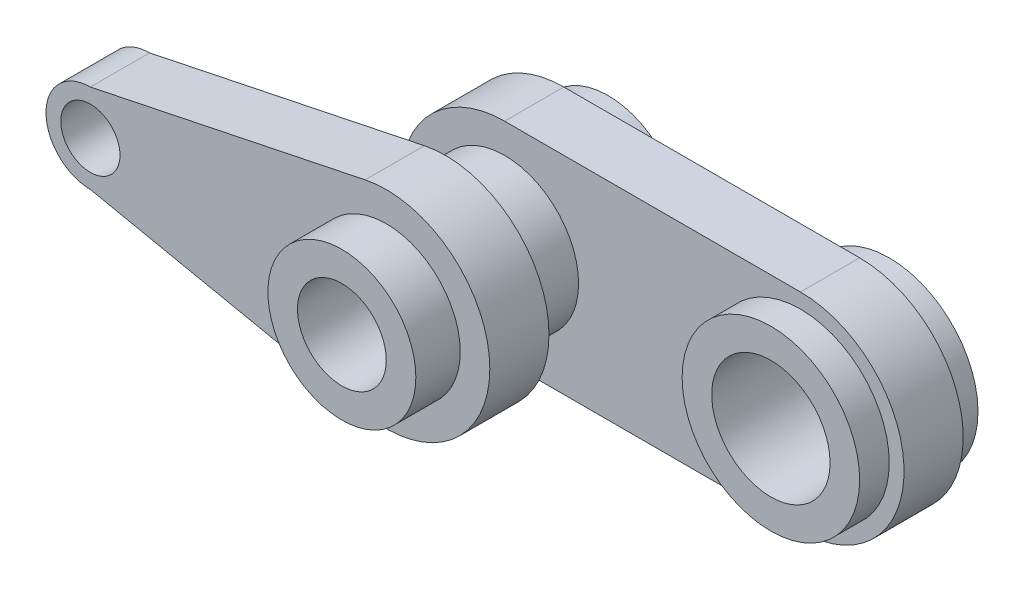
SolidWorks part; units mm, degrees
ref_plane "Front Plane" through (0, 0, 0) normal (0, 0, 1) x (1, 0, 0)
ref_plane "Top Plane" through (0, 0, 0) normal (0, 1, 0) x (1, 0, 0)
ref_plane "Right Plane" through (0, 0, 0) normal (1, 0, 0) x (0, 0, -1)
sketch "Sketch1" plane through (0, 0, 0) normal (0, 0, 1) x (1, 0, 0)
  line L0 (0, 0) -> (170, 0)
  line L1 (170, 0) -> (170, 70)
  line L2 (170, 70) -> (0, 70)
  line L3 (0, 70) -> (0, 0)
  dimension "D1" = 170
  dimension "D2" = 70
extrude "Boss-Extrude1" add sketch "Sketch1" along normal mid plane 20
fillet "Fillet1" 2 edges at (170, 70, 0) (170, 0, 0) type full round first side face at (85, 70, 0) second side face at (85, 0, 0) middle face at (170, 35, 0)
fillet "Fillet2" 2 edges at (0, 0, 0) (0, 70, 0) type full round first side face at (67.5, 0, 0) second side face at (67.5, 70, 0) middle face at (0, 35, 0)
sketch "Sketch2" plane through (0, 0, 10) normal (0, 0, 1) x (1, 0, 0)
  circle A0 centre (135, 35) radius 30
  dimension "D1" = 60
extrude "Boss-Extrude2" add sketch "Sketch2" along normal blind 10 and the other way blind 30
sketch "Sketch3" plane through (0, 0, 10) normal (0, 0, 1) x (1, 0, 0)
  circle A0 centre (35, 35) radius 25
  dimension "D1" = 50
extrude "Boss-Extrude3" add sketch "Sketch3" along normal blind 20 and the other way blind 35
sketch "Sketch4" plane through (0, 0, 30) normal (0, 0, 1) x (1, 0, 0)
  line L0 (-65, 20) -> (27.8905, 0.7297)
  line L1 (-65, 50) -> (27.8905, 69.2703)
  circle A0 centre (35, 35) radius 25
  circle A1 centre (35, 35) radius 35
  arc A2 (-65, 50) -> (-65, 20) centre (-65, 35) ccw
  circle M6 centre (35, 35) radius 25
  dimension "D1" = 50
  dimension "D2" = 70
  dimension "D3" = 30
  dimension "D4" = 100
extrude "Boss-Extrude4" add sketch "Sketch4" along normal blind 20 separate body contours L1 A2 L0 A1 | A1 M6 | A0 region at (-30.1837, 35, 30) region at (0.9899, 35, 30)
sketch "Sketch5" plane through (0, 0, 50) normal (0, 0, 1) x (1, 0, 0)
  circle A0 centre (35, 35) radius 25
  dimension "D1" = 50
extrude "Boss-Extrude5" add sketch "Sketch5" along normal blind 15
sketch "Sketch6" plane through (0, 0, 65) normal (0, 0, 1) x (1, 0, 0)
  circle A0 centre (-65, 35) radius 10
  circle A1 centre (35, 35) radius 15
  circle A2 centre (35, 35) radius 25
  circle A3 centre (135, 35) radius 20
  circle A4 centre (135, 35) radius 30
  dimension "D1" = 20
  dimension "D2" = 30
  dimension "D3" = 50
  dimension "D4" = 40
  dimension "D5" = 60
extrude "Cut-Extrude1" cut sketch "Sketch6" against normal through all contours A1 | A3 | A0
